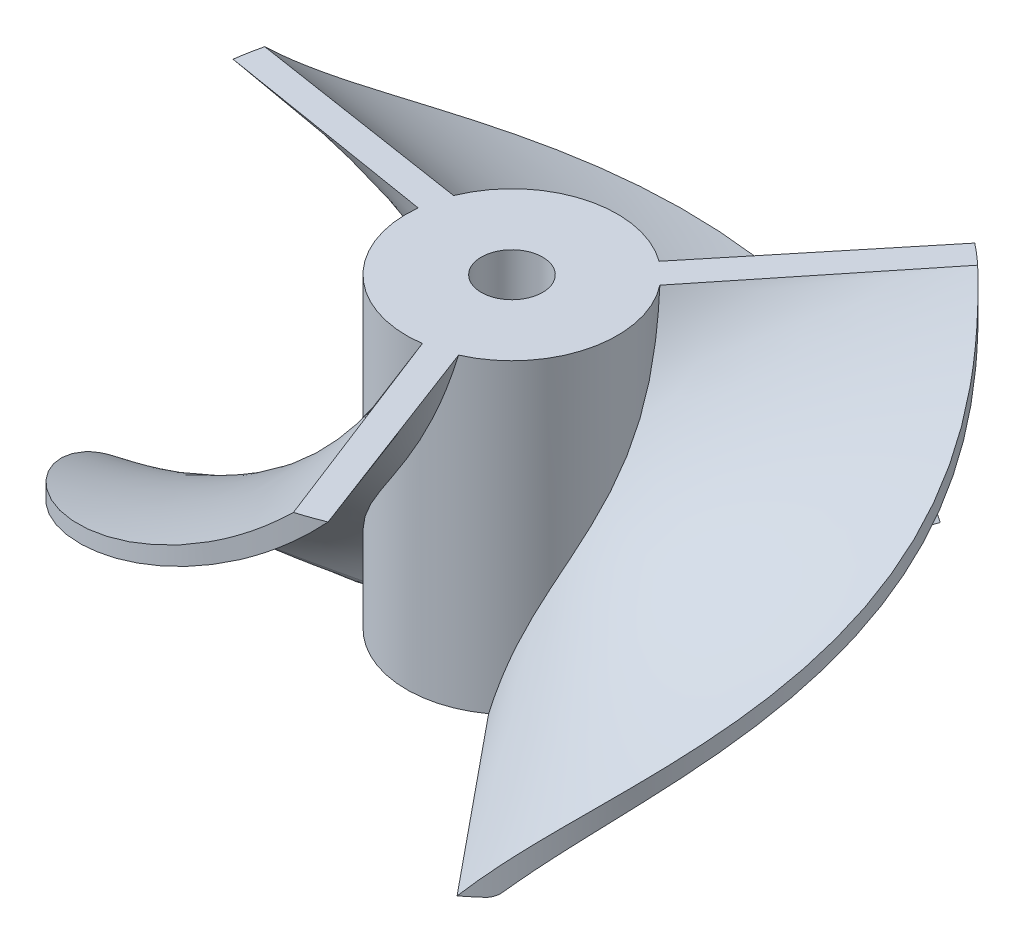
SolidWorks part; units mm, degrees
ref_plane "Ön Düzlem" through (0, 0, 0) normal (0, 0, 1) x (1, 0, 0)
ref_plane "Üst Düzlem" through (0, 0, 0) normal (0, 1, 0) x (1, 0, 0)
ref_plane "Sağ Düzlem" through (0, 0, 0) normal (1, 0, 0) x (0, 0, -1)
ref_plane "Düzlem1" through (45, 0, 0) normal (1, 0, 0) x (0, 0, -1)
sketch "Çizim1" plane through (0, 0, 0) normal (0, 1, 0) x (1, 0, 0)
  circle A0 centre (0, 0) radius 11
  dimension "D1" = 22
extrude "Yükseklik-Ekstrüzyon1" add sketch "Çizim1" along normal blind 32 contours A0
sketch "Çizim2" plane through (0, 0, 0) normal (1, 0, 0) x (0, 0, -1)
  line L4 (-11, 0) -> (11, 0) construction
  line L10 (-1, 0) -> (4, 0)
  line L11 (11, 32) -> (-11, 32) construction
  line L12 (1, 32) -> (-4, 32)
  line L13 (-4, 32) -> (-1, 0)
  line L15 (4, 0) -> (1, 32)
  dimension "D1" = 5
  dimension "D2" = 5
  dimension "D4" = 10
  dimension "D5" = 10
sketch "Çizim4" plane through (45, 0, 0) normal (1, 0, 0) x (0, 0, -1)
  line L0 (56, 32) -> (52, 32)
  line L3 (-1, 0) -> (4, 0) construction
  line L6 (-11, 0) -> (11, 0) construction
  line L7 (11, 32) -> (-11, 32) construction
  line L9 (52, 32) -> (-56, 0)
  line L11 (-56, 0) -> (-52, 0)
  line L12 (56, 32) -> (-52, 0)
  dimension "D1" = 45
  dimension "D3" = 4
  dimension "D4" = 45
loft "Loft1" add profiles "Çizim4", "Çizim2" connector at (45, 0, 52) connector at (0, 0, -4)
ref_axis "Eksen1" through (0, 43.9969, 0) along (0, -1, 0)
fillet "Radyus1" radius 2 1 edges
pattern_circular "Dairesel Kaplama1" count 3 over 360 about axis through (0, 43.9969, 0) along (0, -1, 0) of "Loft1", "Radyus1"
sketch "Çizim5" plane through (0, 0, 0) normal (0, 1, 0) x (1, 0, 0)
  circle A0 centre (0, 0) radius 34.4
  circle A1 centre (0, 0) radius 100
extrude "Kes-Ekstrüzyon1" cut sketch "Çizim5" along normal through all
sketch "Çizim7" plane through (0, 0, 0) normal (0, 1, 0) x (1, 0, 0)
  line L0 (4.8221, 1.5) -> (7, 1.5)
  line L1 (4.8221, -1.5) -> (7, -1.5)
  line L2 (-7, 1.5) -> (-4.8221, 1.5)
  line L4 (-7, 1.5) -> (-7, -1.5)
  line L5 (-7, -1.5) -> (-4.8221, -1.5)
  line L6 (7, 1.5) -> (7, -1.5)
  arc A0 (-4.8221, -1.5) -> (4.8221, -1.5) centre (0, 0) ccw
  arc A1 (4.8221, 1.5) -> (-4.8221, 1.5) centre (0, 0) ccw
  dimension "D1" = 5.05
extrude "Kes-Ekstrüzyon2" cut sketch "Çizim7" along normal blind 12
sketch "Çizim8" plane through (0, 0, 0) normal (0, 1, 0) x (1, 0, 0)
  circle A0 centre (0, 0) radius 3.2
extrude "Kes-Ekstrüzyon3" cut sketch "Çizim8" along normal through all from offset 20
sketch "Çizim9" plane through (0, 0, 0) normal (0, 1, 0) x (1, 0, 0)
  circle A0 centre (0, 0) radius 1.65
extrude "Kes-Ekstrüzyon4" cut sketch "Çizim9" along normal through all
